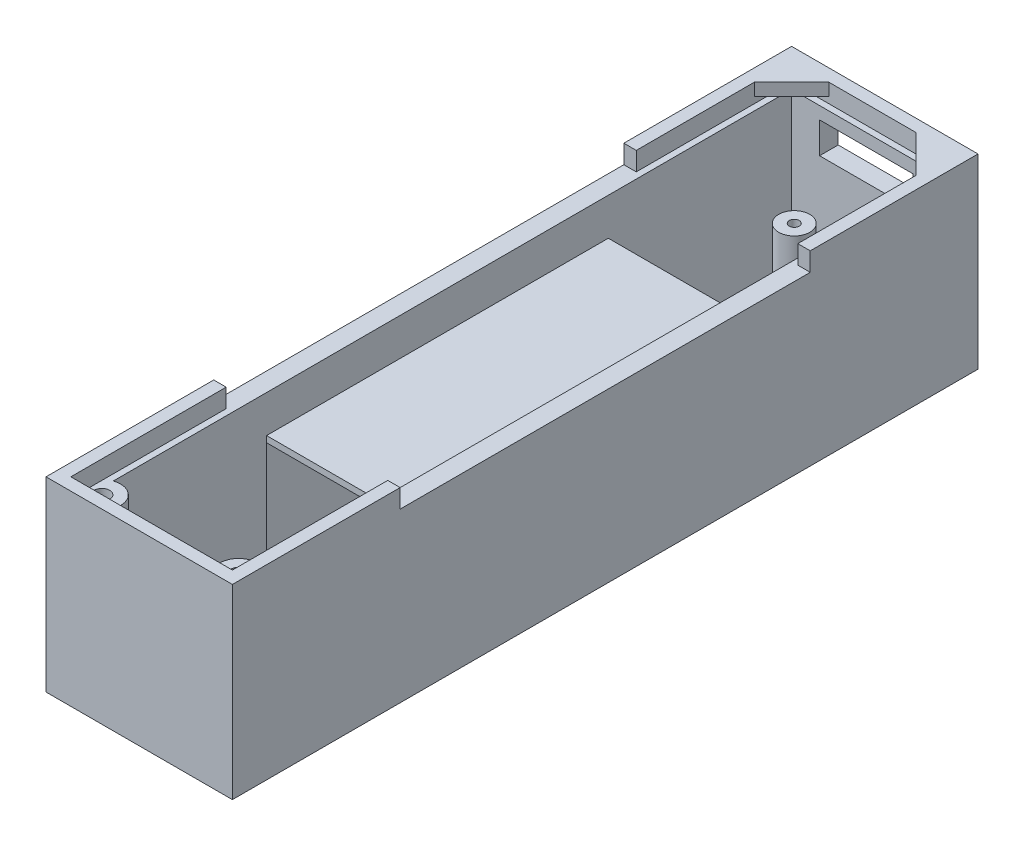
SolidWorks part; units mm, degrees
ref_plane "Front" through (0, 0, 0) normal (0, 0, 1) x (1, 0, 0)
ref_plane "Top" through (0, 0, 0) normal (0, 1, 0) x (1, 0, 0)
ref_plane "Right" through (0, 0, 0) normal (1, 0, 0) x (0, 0, -1)
sketch "Sketch1" plane through (0, 0, 0) normal (0, 1, 0) x (1, 0, 0)
  line L1 (-15, -60) -> (15, -60)
  line L2 (-15, -60) -> (-15, 60)
  line L3 (-15, 60) -> (15, 60)
  line L4 (15, -60) -> (15, 60)
  line L5 (-15, -60) -> (15, 60) construction
  line L6 (-15, 60) -> (15, -60) construction
  point P0 (0, 0)
  dimension "D1" = 120
  dimension "D2" = 30
extrude "Boss-Extrude1" add sketch "Sketch1" along normal blind 30 contours L2 L3 L4 L1
sketch "Sketch3" plane through (0, 30, 0) normal (0, 1, 0) x (1, 0, 0)
  line L1 (-12, -57) -> (12, -57)
  line L2 (-12, -57) -> (-12, 57)
  line L3 (-12, 57) -> (12, 57)
  line L4 (12, -57) -> (12, 57)
  line L5 (-12, -57) -> (12, 57) construction
  line L6 (-12, 57) -> (12, -57) construction
  point P0 (0, 0)
  dimension "D1" = 114
  dimension "D2" = 24
extrude "Cut-Extrude1" cut sketch "Sketch3" against normal blind 27.5
sketch "Sketch4" plane through (0, 30, 0) normal (0, 1, 0) x (1, 0, 0)
  line L1 (-13, -58) -> (13, -58)
  line L2 (-13, -58) -> (-13, 58)
  line L3 (-13, 58) -> (13, 58)
  line L4 (13, -58) -> (13, 58)
  line L5 (-13, -58) -> (13, 58) construction
  line L6 (-13, 58) -> (13, -58) construction
  point P0 (0, 0)
  dimension "D1" = 26
  dimension "D2" = 116
extrude "Cut-Extrude2" cut sketch "Sketch4" against normal blind 3
sketch "Sketch5" plane through (15, 0, 0) normal (1, 0, 0) x (0, 0, -1)
  line L0 (-60, 30) -> (60, 30) construction
  line L1 (-33, 27) -> (33, 27)
  line L2 (-33, 27) -> (-33, 30)
  line L3 (-33, 30) -> (33, 30)
  line L4 (33, 27) -> (33, 30)
  line L5 (-33, 27) -> (33, 30) construction
  line L6 (-33, 30) -> (33, 27) construction
  line L7 (0, 28.5) -> (0, 0) construction
  point P0 (0, 28.5)
  dimension "D1" = 66
  dimension "D2" = 3
extrude "Cut-Extrude3" cut sketch "Sketch5" against normal through all
sketch "Sketch6" plane through (0, 0, 0) normal (0, -1, 0) x (1, 0, 0)
  line L1 (-12.5, -27.5) -> (12.5, -27.5)
  line L2 (-12.5, -27.5) -> (-12.5, 27.5)
  line L3 (-12.5, 27.5) -> (12.5, 27.5)
  line L4 (12.5, -27.5) -> (12.5, 27.5)
  line L5 (-12.5, -27.5) -> (12.5, 27.5) construction
  line L6 (-12.5, 27.5) -> (12.5, -27.5) construction
  point P0 (0, 0)
  dimension "D1" = 25
  dimension "D2" = 55
extrude "Cut-Extrude4" cut sketch "Sketch6" against normal blind 20
sketch "Sketch8" plane through (0, 20, 0) normal (0, -1, 0) x (1, 0, 0)
  line L1 (12, 27.5) -> (-12, 27.5)
  line L2 (12, 27.5) -> (12, -27.5)
  line L3 (12, -27.5) -> (-12, -27.5)
  line L4 (-12, 27.5) -> (-12, -27.5)
  line L5 (12, 27.5) -> (-12, -27.5) construction
  line L6 (12, -27.5) -> (-12, 27.5) construction
  point P0 (0, 0)
extrude "Boss-Extrude2" add sketch "Sketch8" against normal blind 1
sketch "Sketch9" plane through (0, 0, -60) normal (0, 0, -1) x (-1, 0, 0)
  line L0 (0, 0) -> (0, 30) construction
  line L1 (7.5, 25) -> (-7.5, 25)
  line L2 (7.5, 25) -> (7.5, 20)
  line L3 (7.5, 20) -> (-7.5, 20)
  line L4 (-7.5, 25) -> (-7.5, 20)
  line L5 (7.5, 25) -> (-7.5, 20) construction
  line L6 (7.5, 20) -> (-7.5, 25) construction
  line L7 (15, 0) -> (-15, 0) construction
  line L8 (15, 30) -> (-15, 30) construction
  point P0 (0, 22.5)
  dimension "D1" = 5
  dimension "D2" = 15
  dimension "D3" = 5
extrude "Cut-Extrude5" cut sketch "Sketch9" against normal up to surface (3 mm away) up to face at (0, 14.75, -57)
sketch "Sketch10" plane through (0, 2.5, 0) normal (0, 1, 0) x (1, 0, 0)
  line L0 (0, 0) -> (0, 57) construction
  line L1 (12, 57) -> (-12, 57) construction
  line L2 (-12, 42.25) -> (12, 42.25) construction
  line L3 (-12, 57) -> (-12, 27.5) construction
  line L4 (12, 27.5) -> (12, 57) construction
  circle A0 centre (-7.62, 31.455) radius 2.5
  circle A1 centre (-7.62, 53.045) radius 2.5
  circle A2 centre (7.62, 53.045) radius 2.5
  circle A3 centre (7.62, 31.455) radius 2.5
  point P13 (-7.62, 53.045)
  point P16 (7.62, 31.455)
  point P17 (7.62, 53.045)
  dimension "D2" = 5
  dimension "D1" = 21.59
  dimension "D3" = 15.24
extrude "Boss-Extrude3" add sketch "Sketch10" along normal blind 10
sketch "Sketch13" plane through (0, 27, 0) normal (0, 1, 0) x (1, 0, 0)
  line L0 (0, -57) -> (0, -37.9781) construction
  line L1 (-12, -57) -> (12, -57) construction
  line L2 (-12, -27.5) -> (-12, -57) construction
  line L3 (-12, -57) -> (12, -57) construction
  line L5 (-12, -52.1716) -> (-12, -57)
  line L6 (-12, -57) -> (-8.7639, -57)
  line L7 (12, -57) -> (8.7639, -57)
  line L8 (12, -52.1716) -> (12, -57)
  line L9 (-13, -33) -> (-13, -58) construction
  line L10 (-13, -58) -> (13, -58) construction
  arc A0 (-12, -52.1716) -> (-8.7639, -57) centre (-11, -55) cw
  arc A1 (12, -52.1716) -> (8.7639, -57) centre (11, -55) ccw
  dimension "D1" = 3
  dimension "D2" = 2
  dimension "D3" = 3
extrude "Boss-Extrude4" add sketch "Sketch13" against normal up to surface (24.5 mm away) up to face at (0, 2.5, 42.25)
hole_wizard "M2x0.4 Tapped Hole1" positions "Sketch11" profile "Sketch12" tap size "M2x0.4" standard "ANSI Metric"
sketch "Sketch11" plane through (0, 12.5, 0) normal (0, 1, 0) x (1, 0, 0)
  point P0 (-7.62, 31.455)
  point P3 (-7.62, 53.045)
  point P6 (7.62, 53.045)
  point P9 (7.62, 31.455)
sketch "Sketch12" plane through (-7.62, 12.5, -31.455) normal (1, 0, 0) x (0, 0, 1)
  line L0 (0, 0) -> (0, 5.6807)
  line L1 (0, 5.6807) -> (0.8, 5.2)
  line L2 (0.8, 5.2) -> (0.8, 0)
  line L5 (0.8, 0) -> (0, 0)
  line L10 (0, 5.6807) -> (-0.8, 5.2) construction
  line L11 (0, -6.35) -> (0, 107.95) construction
  dimension "Tap Drill Dia." = 1.6
  dimension "Tap Drill Depth" = 5.2
  dimension "Drill Angle" = 118
cosmetic thread "Hole Thread1" parameters "D1"=4, "D2"=2
cosmetic thread "Hole Thread2" parameters "D1"=4, "D2"=2
cosmetic thread "Hole Thread3" parameters "D1"=4, "D2"=2
cosmetic thread "Hole Thread4" parameters "D1"=4, "D2"=2
hole_wizard "Tap Drill for M3x0.5 Tap2" positions "Sketch18" profile "Sketch19" hole size "M3x0.5" standard "ANSI Metric" end condition through all
sketch "Sketch18" plane through (0, 27, 0) normal (0, 1, 0) x (1, 0, 0)
  point P0 (-11, -55)
  point P3 (11, -55)
sketch "Sketch19" plane through (-11, 27, 55) normal (1, 0, 0) x (0, 0, 1)
  line L0 (0, 0) -> (0, 27)
  line L1 (0, 27) -> (1.25, 27)
  line L2 (1.25, 27) -> (1.25, 0)
  line L5 (1.25, 0) -> (0, 0)
  line L11 (0, -6.35) -> (0, 107.95) construction
  dimension "Thru Hole Dia." = 2.5
  dimension "Thru Hole Depth" = 27
sketch "Sketch21" plane through (0, 30, 0) normal (0, 1, 0) x (1, 0, 0)
  line L0 (-13, 52) -> (-7, 58)
  line L1 (-13, 58) -> (-13, 33) construction
  line L2 (13, 58) -> (-13, 58) construction
  line L3 (-7, 58) -> (-13, 58)
  line L4 (-13, 58) -> (-13, 52)
  line L5 (0, 58) -> (0, 52.1711) construction
  line L6 (13, 58) -> (-13, 58) construction
  line L7 (13, 58) -> (13, 52)
  line L8 (7, 58) -> (13, 58)
  line L9 (13, 52) -> (7, 58)
  dimension "D1" = 6
  dimension "D2" = 6
extrude "Boss-Extrude7" add sketch "Sketch21" against normal blind 2
sketch "Sketch22" plane through (0, 2.5, 0) normal (0, 1, 0) x (1, 0, 0)
  line L0 (-8.7639, -57) -> (8.7639, -57) construction
  line L1 (-4, -57) -> (4, -57)
  line L2 (-4, -57) -> (-4, -42)
  line L3 (-4, -42) -> (4, -42)
  line L4 (4, -57) -> (4, -42)
  line L5 (-4, -57) -> (4, -42) construction
  line L6 (-4, -42) -> (4, -57) construction
  line L7 (0, -49.5) -> (0, -57) construction
  point P0 (0, -49.5)
  point P6 (0, 0)
  point P10 (0, 0)
  dimension "D1" = 8
  dimension "D2" = 15
extrude "Cut-Extrude6" cut sketch "Sketch22" against normal through all
